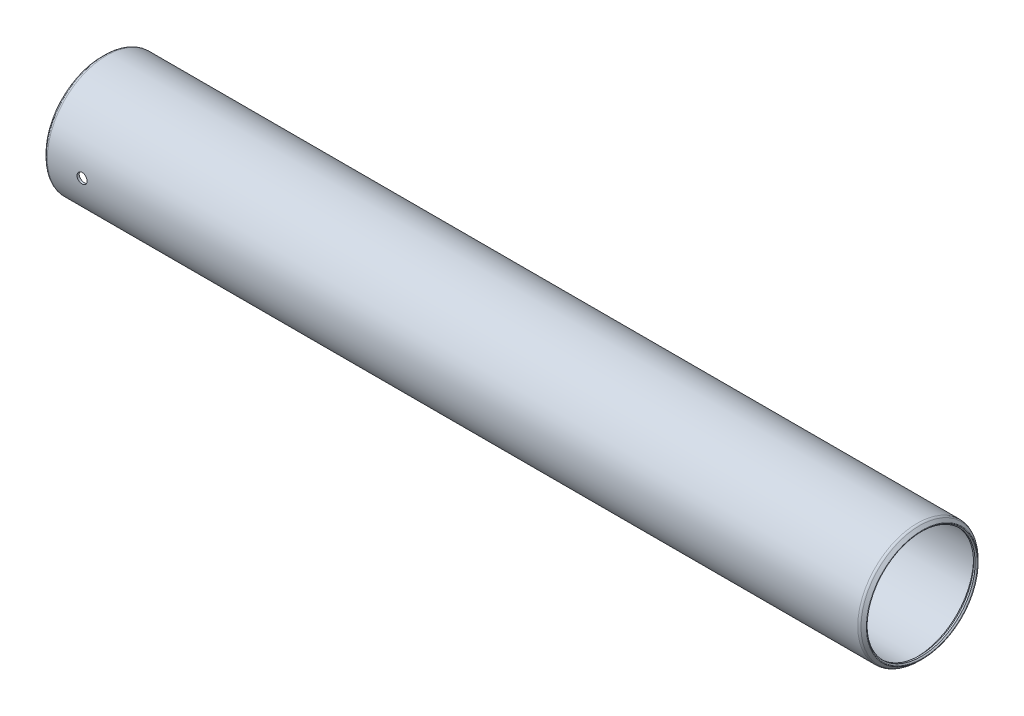
SolidWorks part; units mm, degrees
material "Cast Alloy Steel"
ref_plane "Front Plane" through (0, 0, 0) normal (0, 0, 1) x (1, 0, 0)
ref_plane "Top Plane" through (0, 0, 0) normal (0, 1, 0) x (1, 0, 0)
ref_plane "Right Plane" through (0, 0, 0) normal (1, 0, 0) x (0, 0, -1)
ref_plane "Plane1" through (193.5734, 0, 0) normal (1, 0, 0) x (0, 0, -1)
sketch "Sketch1" plane through (0, 0, 0) normal (0, 0, 1) x (1, 0, 0)
  line L0 (-0.6395, 13.1046) -> (-0.381, 12.846)
  line L1 (-0.381, 12.846) -> (0, 12.846)
  line L2 (0, 12.846) -> (0.762, 13.6081)
  line L3 (0.762, 13.6081) -> (192.8114, 13.6081)
  line L4 (192.8114, 13.6081) -> (193.5734, 12.846)
  line L5 (193.5734, 12.846) -> (193.9544, 12.846)
  line L6 (193.9544, 12.846) -> (194.2129, 13.1046)
  line L7 (194.2129, 13.2842) -> (193.5852, 13.9119)
  line L8 (193.0464, 14.1351) -> (0.527, 14.1351)
  line L9 (-0.0118, 13.9119) -> (-0.6395, 13.2842)
  line L10 (193.5734, 0) -> (0, 0) construction
  arc A0 (-0.6395, 13.2842) -> (-0.6395, 13.1046) centre (-0.5497, 13.1944) ccw
  arc A1 (194.2129, 13.1046) -> (194.2129, 13.2842) centre (194.1231, 13.1944) ccw
  arc A2 (193.5852, 13.9119) -> (193.0464, 14.1351) centre (193.0464, 13.3731) ccw
  arc A3 (0.527, 14.1351) -> (-0.0118, 13.9119) centre (0.527, 13.3731) ccw
revolve "Revolve1" add sketch "Sketch1" angle 360 about L10 reverse direction yes
sketch "Sketch2" plane through (0, 0, 0) normal (0, 0, 1) x (1, 0, 0)
  circle A0 centre (8.763, 0) radius 1.1938
extrude "Cut-Extrude1" cut sketch "Sketch2" along normal blind 14.1351
ref_plane "Plane2" through (96.7867, 0, 0) normal (1, 0, 0) x (0, 0, -1)
ref_plane "cp1 XY" through (96.7867, 0, 0) normal (1, 0, 0) x (0, 0, -1)
ref_plane "cp1 XZ" through (0, 14.1351, 0) normal (0, -1, 0) x (-1, 0, 0)
ref_plane "cp1 YZ" through (0, 0, 0) normal (0, 0, -1) x (-1, 0, 0)
ref_axis "cp1 X" through (96.7867, 14.1351, 80.9) along (0, 0, -1)
ref_axis "cp1 Y" through (96.7867, -50, 0) along (0, 1, 0)
ref_axis "cp1 Z" through (80.9, 14.1351, 0) along (-1, 0, 0)
sketch3d "cp1"
  point P0 (96.7867, 14.1351, 0)
ref_plane "cp2 XY" through (96.7867, 0, 0) normal (1, 0, 0) x (0, 0, -1)
ref_plane "cp2 XZ" through (0, 0, 0) normal (0, -1, 0) x (-1, 0, 0)
ref_plane "cp2 YZ" through (0, 0, -14.1351) normal (0, 0, -1) x (-1, 0, 0)
ref_axis "cp2 X" through (96.7867, 0, 80.9) along (0, 0, -1)
ref_axis "cp2 Y" through (96.7867, -50, -14.1351) along (0, 1, 0)
ref_axis "cp2 Z" through (80.9, 0, -14.1351) along (-1, 0, 0)
sketch3d "cp2"
  point P0 (96.7867, 0, -14.1351)
ref_plane "cp3 XY" through (96.7867, 0, 0) normal (1, 0, 0) x (0, 0, -1)
ref_plane "cp3 XZ" through (0, -14.1351, 0) normal (0, -1, 0) x (-1, 0, 0)
ref_plane "cp3 YZ" through (0, 0, 0) normal (0, 0, -1) x (-1, 0, 0)
ref_axis "cp3 X" through (96.7867, -14.1351, 80.9) along (0, 0, -1)
ref_axis "cp3 Y" through (96.7867, -50, 0) along (0, 1, 0)
ref_axis "cp3 Z" through (80.9, -14.1351, 0) along (-1, 0, 0)
sketch3d "cp3"
  point P0 (96.7867, -14.1351, 0)
ref_plane "cp4 XY" through (96.7867, 0, 0) normal (1, 0, 0) x (0, 0, -1)
ref_plane "cp4 XZ" through (0, 0, 0) normal (0, -1, 0) x (-1, 0, 0)
ref_plane "cp4 YZ" through (0, 0, 14.1351) normal (0, 0, -1) x (-1, 0, 0)
ref_axis "cp4 X" through (96.7867, 0, 80.9) along (0, 0, -1)
ref_axis "cp4 Y" through (96.7867, -50, 14.1351) along (0, 1, 0)
ref_axis "cp4 Z" through (80.9, 0, 14.1351) along (-1, 0, 0)
sketch3d "cp4"
  point P0 (96.7867, 0, 14.1351)
ref_plane "tube_front XY" through (0, 0, 0) normal (1, 0, 0) x (0, 0, -1)
ref_plane "tube_front XZ" through (0, 0, 0) normal (0, -1, 0) x (-1, 0, 0)
ref_plane "tube_front YZ" through (0, 0, 0) normal (0, 0, -1) x (-1, 0, 0)
ref_axis "tube_front X" through (0, 0, 80.9) along (0, 0, -1)
ref_axis "tube_front Y" through (0, -50, 0) along (0, 1, 0)
ref_axis "tube_front Z" through (80.9, 0, 0) along (-1, 0, 0)
sketch3d "tube_front"
  point P0 (0, 0, 0)
ref_plane "tube_rear XY" through (193.5734, 0, 0) normal (1, 0, 0) x (0, 0, -1)
ref_plane "tube_rear XZ" through (0, 0, 0) normal (0, -1, 0) x (-1, 0, 0)
ref_plane "tube_rear YZ" through (0, 0, 0) normal (0, 0, -1) x (-1, 0, 0)
ref_axis "tube_rear X" through (193.5734, 0, 80.9) along (0, 0, -1)
ref_axis "tube_rear Y" through (193.5734, -50, 0) along (0, 1, 0)
ref_axis "tube_rear Z" through (80.9, 0, 0) along (-1, 0, 0)
sketch3d "tube_rear"
  point P0 (193.5734, 0, 0)
